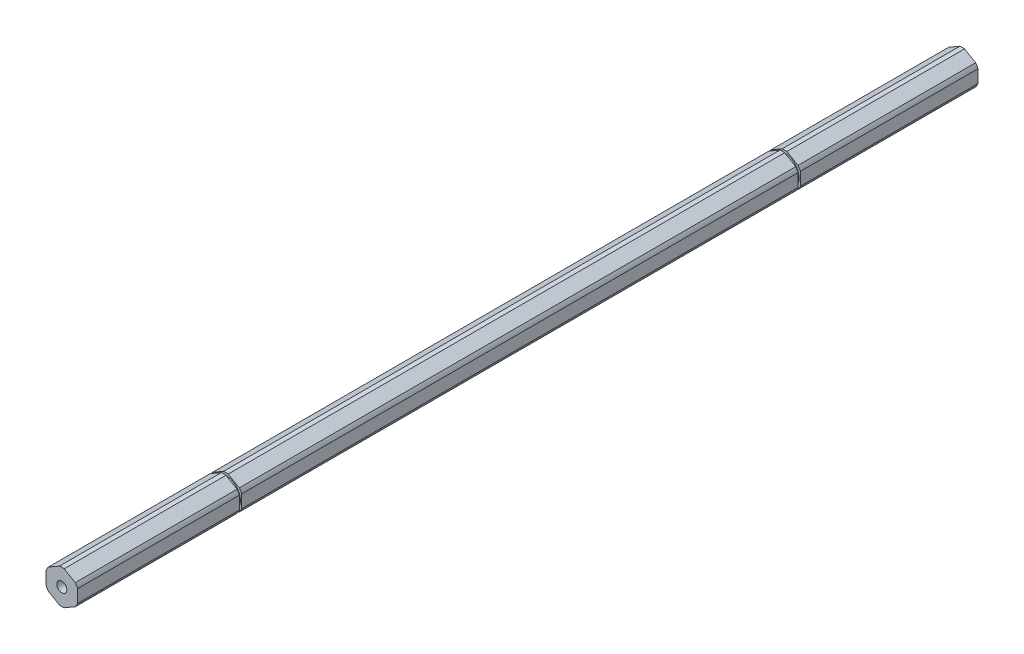
SolidWorks part; units mm, degrees
material "6061-T6 (SS)"
ref_plane "Front Plane" through (0, 0, 0) normal (0, 0, 1) x (1, 0, 0)
ref_plane "Top Plane" through (0, 0, 0) normal (0, 1, 0) x (1, 0, 0)
ref_plane "Right Plane" through (0, 0, 0) normal (1, 0, 0) x (0, 0, -1)
sketch "Sketch1" plane through (0, 0, 0) normal (0, 0, 1) x (1, 0, 0)
  line L1 (0, 7.3323) -> (-6.35, 3.6662)
  line L2 (-6.35, 3.6662) -> (-6.35, -3.6662)
  line L3 (-6.35, -3.6662) -> (0, -7.3323)
  line L4 (0, -7.3323) -> (6.35, -3.6662)
  line L5 (6.35, -3.6662) -> (6.35, 3.6662)
  line L6 (6.35, 3.6662) -> (0, 7.3323)
  circle A0 centre (0, 0) radius 6.35 construction
  circle A1 centre (0, 0) radius 6.858
  dimension "D1" = 12.7
  dimension "D2" = 13.716
extrude "Boss-Extrude1" add sketch "Sketch1" along normal mid plane 361.95 contours L5 A1 L6 L1 L2 L3 L4 region at (0, 0, 0)
sketch "Sketch2" plane through (0, 0, 180.975) normal (0, 0, 1) x (1, 0, 0)
  circle A0 centre (0, 0) radius 2.0193
  dimension "D1" = 4.0386
extrude "Cut-Extrude1" cut sketch "Sketch2" against normal through all
sketch "Sketch4" plane through (0, 0, 0) normal (0, 1, 0) x (1, 0, 0)
  line L0 (-2.0193, -180.975) -> (2.0193, -180.975) construction
  line L5 (-0.9317, -180.975) -> (0.9317, -180.975) construction
  line L7 (9.0297, 109.5502) -> (5.8547, 109.5502)
  line L8 (9.0297, 109.5502) -> (9.0297, 108.6612)
  line L9 (9.0297, 108.6612) -> (5.8547, 108.6612)
  line L10 (5.8547, 109.5502) -> (5.8547, 108.6612)
  line L11 (5.8547, -115.9002) -> (9.0297, -115.9002)
  line L12 (0, 180.975) -> (0, -180.975) construction
  line L13 (2.0193, 180.975) -> (-2.0193, 180.975) construction
  line L14 (5.8547, -115.9002) -> (5.8547, -115.0112)
  line L15 (5.8547, -115.0112) -> (9.0297, -115.0112)
  line L16 (9.0297, -115.9002) -> (9.0297, -115.0112)
  dimension "D1" = 0.889
  dimension "D2" = 361.95
  dimension "D3" = 5.8547
  dimension "D4" = 71.4248
  dimension "D5" = 3.175
  dimension "D6" = 3.175
  dimension "D7" = 0.889
  dimension "D8" = 65.0748
revolve "Cut-Revolve4" cut sketch "Sketch4" angle 360 about L12
equation "\"D1@Boss-Extrude1\"=14.25"
